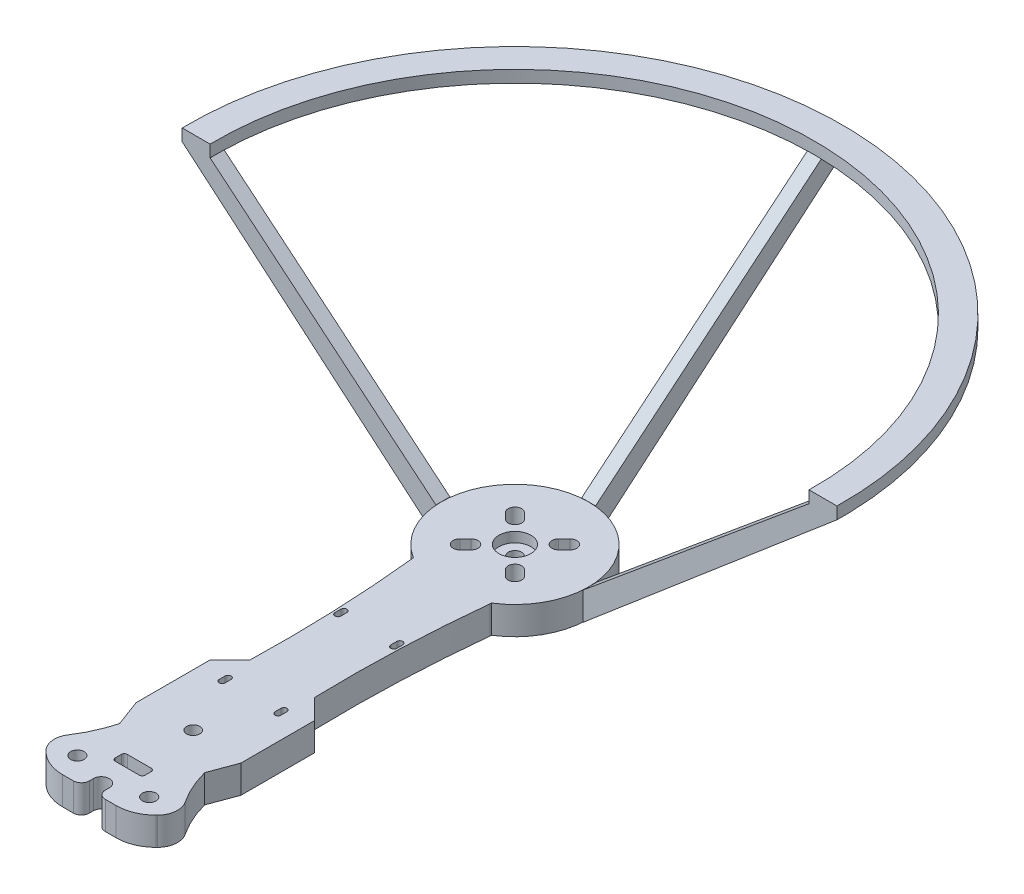
SolidWorks part; units mm, degrees
ref_plane "Front Plane" through (0, 0, 0) normal (0, 0, 1) x (1, 0, 0)
ref_plane "Top Plane" through (0, 0, 0) normal (0, 1, 0) x (1, 0, 0)
ref_plane "Right Plane" through (0, 0, 0) normal (1, 0, 0) x (0, 0, -1)
sketch "Sketch1" plane through (0, 0, 0) normal (0, 1, 0) x (1, 0, 0)
  line L1 (10, -38) -> (-10, -38)
  line L2 (10, -38) -> (10, 38)
  line L3 (10, 38) -> (-10, 38)
  line L4 (-10, -38) -> (-10, 38)
  line L5 (10, -38) -> (-10, 38) construction
  line L6 (10, 38) -> (-10, -38) construction
  point P0 (0, 0)
  dimension "D1" = 20
  dimension "D2" = 76
extrude "Boss-Extrude1" add sketch "Sketch1" along normal blind 7
sketch "Sketch2" plane through (0, 7, 0) normal (0, 1, 0) x (1, 0, 0)
  line L0 (10, 38) -> (-10, 38) construction
  line L1 (9, 69.1769) -> (-9, 69.1769)
  line L2 (-9, 69.1769) -> (-18, 53.5885)
  line L3 (-18, 53.5885) -> (-9, 38)
  line L4 (-9, 38) -> (9, 38)
  line L5 (9, 38) -> (18, 53.5885)
  line L6 (18, 53.5885) -> (9, 69.1769)
  line L7 (0, 43.2469) -> (0, 36.9227) construction
  line L8 (10, 38) -> (10, 39.7321)
  line L9 (10, 38) -> (9, 38)
  line L10 (-10, 38) -> (-9, 38)
  line L11 (-10, 38) -> (-10, 39.7321)
  line L12 (-9, 38) -> (-18, 53.5885)
  line L13 (-9, 38) -> (-18, 53.5885)
  circle A0 centre (0, 53.5885) radius 15.5885 construction
  point P13 (0, 38)
  dimension "D1" = 18
extrude "Boss-Extrude2" add sketch "Sketch2" against normal up to surface (7 mm away) up to face at (0, 0, 0)
sketch "Sketch3" plane through (0, 7, 0) normal (0, 1, 0) x (1, 0, 0)
  line L0 (-6.8943, 46.6942) -> (-5.4801, 48.1084) construction
  line L3 (-8.0964, 47.8962) -> (-6.6822, 49.3105)
  line L6 (-5.6922, 45.4921) -> (-4.278, 46.9063)
  line L9 (0, 28.0527) -> (0, 36.7379) construction
  line L12 (-6.8943, 60.4827) -> (-5.4801, 59.0685) construction
  line L13 (-5.6922, 61.6848) -> (-4.278, 60.2706)
  line L14 (-8.0964, 59.2807) -> (-6.6822, 57.8665)
  line L15 (6.8943, 60.4827) -> (5.4801, 59.0685) construction
  line L16 (8.0964, 59.2807) -> (6.6822, 57.8665)
  line L17 (5.6922, 61.6848) -> (4.278, 60.2706)
  line L18 (6.8943, 46.6942) -> (5.4801, 48.1084) construction
  line L19 (5.6922, 45.4921) -> (4.278, 46.9063)
  line L20 (8.0964, 47.8962) -> (6.6822, 49.3105)
  circle A9 centre (0, 53.5885) radius 8.75 construction
  arc A10 (-8.0964, 47.8962) -> (-5.6922, 45.4921) centre (-6.8943, 46.6942) ccw
  arc A11 (-4.278, 46.9063) -> (-6.6822, 49.3105) centre (-5.4801, 48.1084) ccw
  arc A12 (-5.6922, 61.6848) -> (-8.0964, 59.2807) centre (-6.8943, 60.4827) ccw
  arc A13 (-6.6822, 57.8665) -> (-4.278, 60.2706) centre (-5.4801, 59.0685) ccw
  arc A14 (8.0964, 59.2807) -> (5.6922, 61.6848) centre (6.8943, 60.4827) ccw
  arc A15 (4.278, 60.2706) -> (6.6822, 57.8665) centre (5.4801, 59.0685) ccw
  arc A16 (5.6922, 45.4921) -> (8.0964, 47.8962) centre (6.8943, 46.6942) ccw
  arc A17 (6.6822, 49.3105) -> (4.278, 46.9063) centre (5.4801, 48.1084) ccw
  point P4 (-6.1872, 47.4013)
  point P11 (-7.3893, 48.6034)
  point P19 (-6.1872, 59.7756)
  point P26 (6.1872, 59.7756)
  point P33 (6.1872, 47.4013)
  dimension "D1" = 17.5
  dimension "D3" = 3.4
  dimension "D4" = 45
  dimension "D2" = 2
  dimension "D5" = 4
extrude "Cut-Extrude1" cut sketch "Sketch3" against normal through all
sketch "Sketch4" plane through (0, 7, 0) normal (0, 1, 0) x (1, 0, 0)
  circle A0 centre (0, 53.5885) radius 4
  dimension "D1" = 8
extrude "Cut-Extrude2" [suppressed] cut sketch "Sketch4" against normal blind 2
sketch "Sketch5" plane through (0, 7, 0) normal (0, 1, 0) x (1, 0, 0)
  line L0 (0, -38) -> (0, -53) construction
  line L1 (-10, -38) -> (10, -38) construction
  line L2 (10, -38) -> (-10, -38)
  line L3 (-10, -38) -> (-25, -53)
  line L4 (10, -38) -> (25, -53)
  line L10 (-25, -53) -> (25, -53)
  dimension "D1" = 45
  dimension "D2" = 15
extrude "Boss-Extrude3" add sketch "Sketch5" against normal up to surface (7 mm away) up to face at (6.1872, 0, -47.4013)
hole_wizard "CSK for M3 Flat Head Machine Screw1" positions "Sketch6" profile "Sketch7" countersink size "M3" standard "ANSI Metric" end condition through all
sketch "Sketch6" plane through (0, 0, 0) normal (0, -1, 0) x (-1, 0, 0)
  line L0 (0, -53.2272) -> (0, -12.2793) construction
  line L2 (-25, -53) -> (25, -53) construction
  point P0 (9, -47)
  point P7 (-9, -47)
  dimension "D1" = 18
  dimension "D2" = 6
sketch "Sketch7" plane through (-9, 0, 47) normal (1, 0, 0) x (0, 0, -1)
  line L0 (0, 0) -> (0, 7)
  line L1 (0, 7) -> (1.7, 7)
  line L2 (1.7, 7) -> (1.7, 1.45)
  line L3 (1.7, 1.45) -> (3.15, 0)
  line L5 (3.15, 0) -> (0, 0)
  line L6 (-1.7, 1.45) -> (-3.15, 0) construction
  line L11 (0, -6.35) -> (0, 107.95) construction
  dimension "Thru Hole Dia." = 3.4
  dimension "Thru Hole Depth" = 7
  dimension "Near C'Sink Dia." = 6.3
  dimension "Near C'Sink Angle" = 90
chamfer "Chamfer3" distance 10 angle 45 2 edges at (-25, 3.5, 53) (25, 3.5, 53) first distance on face at (-17.5, 3.5, 45.5) first distance on face at (17.5, 3.5, 45.5)
chamfer "Chamfer4" distance 3 angle 45 2 edges at (-17.9289, 3.5, 53) (17.9289, 3.5, 53)
hole_wizard "Ø3.3 (3.3) Diameter Hole1" positions "Sketch9" profile "Sketch10" hole size "Ø3.3" standard "ANSI Metric" end condition through all
sketch "Sketch9" plane through (0, 0, 0) normal (0, -1, 0) x (-1, 0, 0)
  line L0 (0, 0) -> (0, -27) construction
  line L2 (9, -47) -> (-9, -47) construction
  point P0 (0, -27)
  dimension "D1" = 20
sketch "Sketch10" plane through (0, 0, 27) normal (1, 0, 0) x (0, 0, -1)
  line L0 (0, 0) -> (0, 7)
  line L1 (0, 7) -> (1.65, 7)
  line L2 (1.65, 7) -> (1.65, 0)
  line L5 (1.65, 0) -> (0, 0)
  line L11 (0, -6.35) -> (0, 107.95) construction
  dimension "Thru Hole Dia." = 3.3
  dimension "Thru Hole Depth" = 7
sketch "Sketch12" plane through (0, 7, 0) normal (0, 1, 0) x (1, 0, 0)
  line L0 (-17.9289, -45.9289) -> (-10, -32.1956)
  line L1 (-10, 39.7321) -> (-10, -38) construction
  line L2 (-10, -32.1956) -> (-10, -38)
  line L3 (-10, -38) -> (-17.9289, -45.9289)
  line L4 (0, -31.1921) -> (0, -40.6137) construction
  line L5 (10, -38) -> (17.9289, -45.9289)
  line L6 (10, -32.1956) -> (10, -38)
  line L7 (17.9289, -45.9289) -> (10, -32.1956)
  dimension "D1" = 30
extrude "Boss-Extrude4" add sketch "Sketch12" against normal through all
sketch "Sketch13" plane through (0, 0, 0) normal (0, -1, 0) x (1, 0, 0)
  line L0 (-17.9289, 45.9289) -> (-10.8579, 53)
  line L1 (14.9289, 53) -> (-14.9289, 53) construction
  line L2 (-14.9289, 53) -> (-17.9289, 50) construction
  line L3 (-10.8579, 53) -> (-14.9289, 53)
  line L4 (-14.9289, 53) -> (-17.9289, 50)
  line L5 (-17.9289, 50) -> (-17.9289, 45.9289)
  line L6 (0, 61.138) -> (0, 56.7948) construction
  line L7 (17.9289, 50) -> (17.9289, 45.9289)
  line L8 (14.9289, 53) -> (17.9289, 50)
  line L9 (10.8579, 53) -> (14.9289, 53)
  line L10 (17.9289, 45.9289) -> (10.8579, 53)
extrude "Cut-Extrude3" cut sketch "Sketch13" against normal through all
hole_wizard "Ø3.3 (3.3) Diameter Hole2" positions "Sketch15" profile "Sketch16" hole size "Ø3.3" standard "ANSI Metric" end condition through all
sketch "Sketch15" plane through (0, 7, 0) normal (0, 1, 0) x (1, 0, 0)
  point P0 (0, 53.5885)
sketch "Sketch16" plane through (0, 7, -53.5885) normal (1, 0, 0) x (0, 0, 1)
  line L0 (0, 0) -> (0, 7)
  line L1 (0, 7) -> (1.65, 7)
  line L2 (1.65, 7) -> (1.65, 0)
  line L5 (1.65, 0) -> (0, 0)
  line L11 (0, -6.35) -> (0, 107.95) construction
  dimension "Thru Hole Dia." = 3.3
  dimension "Thru Hole Depth" = 7
sketch "Sketch17" plane through (0, 7, 0) normal (0, 1, 0) x (1, 0, 0)
  line L0 (0, 43.1092) -> (0, 35.1505) construction
  line L1 (-6.25, 15.5) -> (-7.75, 18.5) construction
  line L2 (6.25, 18.5) -> (7.75, 18.5)
  line L3 (6.25, 18.5) -> (6.25, 15.5)
  line L4 (6.25, 15.5) -> (7.75, 15.5)
  line L5 (7.75, 18.5) -> (7.75, 15.5)
  line L6 (6.25, 18.5) -> (7.75, 15.5) construction
  line L7 (6.25, 15.5) -> (7.75, 18.5) construction
  line L8 (-6.25, 18.5) -> (-7.75, 15.5) construction
  line L9 (-7.75, 18.5) -> (-7.75, 15.5)
  line L10 (-6.25, 15.5) -> (-7.75, 15.5)
  line L11 (-6.25, 18.5) -> (-6.25, 15.5)
  line L12 (-6.25, 18.5) -> (-7.75, 18.5)
  line L13 (-6.3154, 6) -> (6.4912, 6) construction
  line L14 (7, 17) -> (-7, 17) construction
  point P3 (7, 17)
  point P12 (-7, 17)
  dimension "D1" = 1.5
  dimension "D2" = 3
  dimension "D3" = 14
  dimension "D4" = 17
extrude "Cut-Extrude5" cut sketch "Sketch17" against normal through all
hole_wizard "Ø4.0 (4) Diameter Hole1" positions "Sketch19" profile "Sketch20" hole size "Ø4.0" standard "ANSI Metric" end condition through all
sketch "Sketch19" plane through (0, 0, 0) normal (0, -1, 0) x (-1, 0, 0)
  line L1 (0, -53) -> (0, -50) construction
  line L2 (-10.8579, -53) -> (10.8579, -53) construction
  point P6 (0, -50)
  dimension "D1" = 3
sketch "Sketch20" plane through (0, 0, 50) normal (1, 0, 0) x (0, 0, -1)
  line L0 (0, 0) -> (0, 7)
  line L1 (0, 7) -> (2, 7)
  line L2 (2, 7) -> (2, 0)
  line L5 (2, 0) -> (0, 0)
  line L11 (0, -6.35) -> (0, 107.95) construction
  dimension "Thru Hole Dia." = 4
  dimension "Thru Hole Depth" = 7
chamfer "Chamfer5" [suppressed] distance 0.5 angle 60
sketch "Sketch22" plane through (0, 7, 0) normal (0, 1, 0) x (1, 0, 0)
  line L0 (8, 3.7682) -> (10, 3.7682) construction
  line L1 (10, -32.1956) -> (10, 39.7321) construction
  line L2 (0, 13.8796) -> (0, 7.1431) construction
  line L3 (10, 39.7321) -> (10, -32.1956)
  line L4 (-8, 3.7682) -> (-10, 3.7682) construction
  line L5 (-10, 39.7321) -> (-10, -32.1956)
  spline S0 degree 2 poles (10, -32.1956) (6, 3.7682) (10, 39.7321) knots 0 0 0 1 1 1
  spline S1 degree 2 poles (-10, -32.1956) (-6, 3.7682) (-10, 39.7321) knots 0 0 0 1 1 1
  dimension "D1" = 2
extrude "Cut-Extrude7" cut sketch "Sketch22" against normal through all
fillet "Fillet1" radius 10 4 edges at (-10, 3.5, -39.7321) (10, 3.5, -39.7321) (-10, 3.5, 32.1956) (10, 3.5, 32.1956)
fillet "Fillet4" radius 10 2 edges at (-10.8579, 3.5, 53) (10.8579, 3.5, 53)
sketch "Sketch24" plane through (0, 7, 0) normal (0, 1, 0) x (1, 0, 0)
  circle A0 centre (0, 53.5885) radius 4
  dimension "D1" = 8
extrude "Cut-Extrude9" cut sketch "Sketch24" against normal blind 2.5
sketch "Sketch25" [suppressed] plane through (0, 3.5, 0) normal (0, 1, 0) x (1, 0, 0)
  line L1 (3.2332, 54.5885) -> (1.6166, 57.3885)
  line L2 (1.6166, 57.3885) -> (-1.6166, 57.3885)
  line L3 (-1.6166, 57.3885) -> (-3.2332, 54.5885)
  line L4 (-3.2332, 54.5885) -> (-1.6166, 51.7885)
  line L5 (-1.6166, 51.7885) -> (1.6166, 51.7885)
  line L6 (1.6166, 51.7885) -> (3.2332, 54.5885)
  circle A0 centre (0, 54.5885) radius 2.8 construction
  dimension "D1" = 5.6
extrude "Cut-Extrude10" [suppressed] cut sketch "Sketch25" against normal blind 2.5
sketch "Sketch26" plane through (0, 7, 0) normal (0, 1, 0) x (1, 0, 0)
  line L0 (13.7868, -50.0711) -> (17.9289, -45.9289) construction
  line L1 (17.1511, -46.7067) -> (17.9289, -45.9289)
  line L2 (17.9289, -45.9289) -> (9.77, -30.0643)
  line L3 (13.8495, -37.9966) -> (12.0709, -38.9113) construction
  line L4 (0, -39.6423) -> (0, -36.9879) construction
  line L5 (-13.8495, -37.9966) -> (-12.0709, -38.9113) construction
  line L6 (-17.9289, -45.9289) -> (-9.77, -30.0643)
  line L7 (-17.1511, -46.7067) -> (-17.9289, -45.9289)
  arc A0 (9.77, -30.0643) -> (11.0554, -34.0237) centre (19.7157, -29.0237) ccw construction
  parabola Q7 (9.77, 37.6007) -> (9.77, -30.0643) focus (169.6747, 3.7682) apex (8, 3.7682) construction
  spline S0 degree 3 poles (9.77, -30.0643) (10.3807, -35.9011) (12.9222, -42.4779) (17.1511, -46.7067) knots 0 0 0 0 1 1 1 1
  spline S1 degree 3 poles (-9.77, -30.0643) (-10.3807, -35.9011) (-12.9222, -42.4779) (-17.1511, -46.7067) knots 0 0 0 0 1 1 1 1
  dimension "D1" = 1.1
  dimension "D2" = 2
extrude "Cut-Extrude11" cut sketch "Sketch26" against normal through all
fillet "Fillet6" radius 5 2 edges at (-17.1511, 3.5, 46.7067) (17.1511, 3.5, 46.7067)
sketch "Sketch27" plane through (0, 0, 0) normal (0, -1, 0) x (1, 0, 0)
  line L0 (0, -41.8385) -> (0, -8.9192) construction
  line L1 (4, -41.8385) -> (-4, -41.8385)
  line L2 (4, -41.8385) -> (4, 24)
  line L3 (4, 24) -> (-4, 24)
  line L4 (-4, -41.8385) -> (-4, 24)
  line L5 (4, -41.8385) -> (-4, 24) construction
  line L6 (4, 24) -> (-4, -41.8385) construction
  line L7 (2.1644, 24) -> (8.503, 34)
  line L8 (8.503, 34) -> (10.4529, 34)
  line L9 (9.77, 30.0643) -> (4, 18.1842)
  line L10 (-9.77, 30.0643) -> (-4, 18.1842)
  line L11 (-8.503, 34) -> (-10.4529, 34)
  line L12 (-2.1644, 24) -> (-8.503, 34)
  arc A0 (-2.9037, 25.1664) -> (3.3528, 25.8748) centre (0.0525, 27.0402) ccw
  spline S0 degree 3 poles (9.77, 30.0643) (10.2443, 34.5975) (11.8833, 39.5771) (14.5729, 43.5564) knots 0 0 0 0 0.776665 0.776665 0.776665 0.776665 construction
  spline S2 degree 3 poles (-9.77, 30.0643) (-10.2443, 34.5975) (-11.8833, 39.5771) (-14.5729, 43.5564) knots 0 0 0 0 0.776665 0.776665 0.776665 0.776665
  spline S3 degree 3 poles (957.257, 3909.3873) (-557.8084, -4132.4571) (127.9512, 4231.1248) (418.084, -3925.1081) knots -10.727138 -10.727138 -10.727138 -10.727138 11.282901 11.282901 11.282901 11.282901 only from (9.77, 30.0643) to (14.5729, 43.5564)
  spline S4 degree 3 poles (9.77, 30.0643) (10.2443, 34.5975) (11.8833, 39.5771) (14.5729, 43.5564) knots 0 0 0 0 0.776665 0.776665 0.776665 0.776665
  point P0 (0, -8.9192)
  point P19 (0, -44.8385)
  spline M15 degree 3 poles (-17.1511, 46.7067) (-12.9222, 42.4779) (-10.3807, 35.9011) (-9.77, 30.0643) knots 0 0 0 0 1 1 1 1 only from (-14.5729, 43.5564) to (-9.77, 30.0643)
  spline M25 degree 3 poles (9.77, 30.0643) (10.3807, 35.9011) (12.9222, 42.4779) (17.1511, 46.7067) knots 0 0 0 0 1 1 1 1 only from (9.77, 30.0643) to (14.5729, 43.5564)
  dimension "D2" = 8
  dimension "D3" = 0
  dimension "D4" = 3
  dimension "D6" = 10
  dimension "D7" = 25.905
extrude "Boss-Extrude5" [suppressed] add sketch "Sketch27" along normal blind 5 contours L3 L12 L11 L10 L4 M15 | L9 L8 L7 L3 L2 M25 | L4 L1 L2 L3 | A0 L3 L7
chamfer "Chamfer6" [suppressed] distance 5 angle 45
chamfer "Chamfer7" [suppressed] distance 1.1 angle 60
sketch "Sketch28" plane through (0, 0, 0) normal (0, -1, 0) x (1, 0, 0)
  line L1 (-6.25, -15.5) -> (6.25, -15.5)
  line L2 (-6.25, -15.5) -> (-6.25, -18.5)
  line L3 (-6.25, -18.5) -> (6.25, -18.5)
  line L4 (6.25, -15.5) -> (6.25, -18.5)
extrude "Cut-Extrude12" [suppressed] cut sketch "Sketch28" along normal blind 2
fillet "Fillet7" [suppressed] radius 1
sketch "Sketch29" plane through (0, 0, 0) normal (0, -1, 0) x (1, 0, 0)
  line L1 (-6.25, -15.5) -> (6.25, -15.5)
  line L2 (-6.25, -15.5) -> (-6.25, -18.5)
  line L3 (-6.25, -18.5) -> (6.25, -18.5)
  line L4 (6.25, -15.5) -> (6.25, -18.5)
extrude "Cut-Extrude13" [suppressed] cut sketch "Sketch29" against normal blind 2
sketch "Sketch30" plane through (0, 0, 0) normal (0, -1, 0) x (1, 0, 0)
  line L0 (4.5, 38.6766) -> (4.5, -37.6008)
  line L1 (0, 13.6383) -> (0, -11.8344) construction
  line L2 (-4.5, 38.6766) -> (-4.5, -37.6008)
  line L3 (4.5, -37.6008) -> (9.77, -37.6008)
  line L5 (-4.5, -37.6008) -> (-9.77, -37.6008)
  line L7 (11.9725, 38.6766) -> (4.5, 38.6766)
  line L8 (-11.9725, 38.6766) -> (-4.5, 38.6766)
  arc A0 (9.77, -37.6007) -> (11.0554, -41.5601) centre (19.7157, -36.5601) ccw construction
  parabola Q1 (-9.77, -37.6008) -> (-9.77, 30.0643) focus (-232.0942, -2.8465) apex (-8.494, -1.93)
  parabola Q3 (9.77, -37.6008) -> (9.77, 30.0643) focus (232.0942, -2.8465) apex (8.494, -1.93)
  parabola Q5 (9.77, -37.6007) -> (9.77, 30.0643) focus (169.6747, -3.7682) apex (8, -3.7682) construction
  spline S1 degree 3 poles (-9.77, 30.0643) (-10.2443, 34.5975) (-11.8833, 39.5771) (-14.5729, 43.5564) knots 0 0 0 0 0.776665 0.776665 0.776665 0.776665
  spline S2 degree 3 poles (957.257, 3909.3873) (-557.8084, -4132.4571) (127.9512, 4231.1248) (418.084, -3925.1081) knots -10.727138 -10.727138 -10.727138 -10.727138 11.282901 11.282901 11.282901 11.282901 only from (9.77, 30.0643) to (14.5729, 43.5564)
  spline S3 degree 3 poles (9.77, 30.0643) (10.2443, 34.5975) (11.8833, 39.5771) (14.5729, 43.5564) knots 0 0 0 0 0.776665 0.776665 0.776665 0.776665
  line M6 (-7.75, -18.5) -> (-7.75, -15.5)
  line M8 (7.75, -15.5) -> (7.75, -18.5)
  spline M13 degree 3 poles (-17.1511, 46.7067) (-12.9222, 42.4779) (-10.3807, 35.9011) (-9.77, 30.0643) knots 0 0 0 0 1 1 1 1 only from (-14.5729, 43.5564) to (-9.77, 30.0643)
  spline M14 degree 2 poles (-10, 32.1956) (-6, -3.7682) (-10, -39.7321) knots 0 0 0 1 1 1 only from (-9.77, 30.0643) to (-9.77, -37.6007)
  arc M15 (-9.77, -37.6007) -> (-11.0554, -41.5601) centre (-19.7157, -36.5601) cw
  arc M21 (11.0554, -41.5601) -> (9.77, -37.6007) centre (19.7157, -36.5601) cw
  spline M22 degree 2 poles (10, -39.7321) (6, -3.7682) (10, 32.1956) knots 0 0 0 1 1 1 only from (9.77, -37.6007) to (9.77, 30.0643)
  spline M23 degree 3 poles (9.77, 30.0643) (10.3807, 35.9011) (12.9222, 42.4779) (17.1511, 46.7067) knots 0 0 0 0 1 1 1 1 only from (9.77, 30.0643) to (14.5729, 43.5564)
  dimension "D1" = 9
  dimension "D3" = 0
extrude "Boss-Extrude6" [suppressed] add sketch "Sketch30" along normal blind 4 contours Q3 L7 L0 L3 M22 M23 M8 M21 | Q1 L5 L2 L8 M14 M15 M6 M13
fillet "Fillet8" radius 0.75 8 edges at (7.75, 3.5, -18.5) (6.25, 3.5, -18.5) (7.75, 3.5, -15.5) (6.25, 3.5, -15.5) (-7.75, 3.5, -18.5) (-7.75, 3.5, -15.5) (-6.25, 3.5, -15.5) (-6.25, 3.5, -18.5)
chamfer "Chamfer9" [suppressed] distance 1 angle 60
chamfer "Chamfer10" [suppressed] distance 0.7 angle 60
sketch "Sketch32" plane through (0, 0, 0) normal (0, -1, 0) x (1, 0, 0)
  line L0 (2, 50) -> (2, 53)
  line L1 (6.7157, 53) -> (-6.7157, 53) construction
  line L2 (2, 53) -> (-2, 53)
  line L3 (-2, 53) -> (-2, 50)
  circle A0 centre (0, 50) radius 2 construction
  arc A1 (-2, 50) -> (2, 50) centre (0, 50) cw
extrude "Cut-Extrude14" cut sketch "Sketch32" against normal through all
fillet "Fillet10" radius 2 2 edges at (2, 3.5, 53) (-2, 3.5, 53)
sketch "Sketch33" plane through (0, 7, 0) normal (0, 1, 0) x (1, 0, 0)
  line L0 (-13.113, -28.1513) -> (-10.6516, -34.7802)
  line L1 (-13.113, -28.1513) -> (-13.113, -9.7802)
  line L2 (-13.113, -9.7802) -> (-8.113, -4.7802)
  line L3 (-10.6516, -34.7802) -> (-8.6702, -31.1191)
  line L4 (-8.6702, -31.1191) -> (-8.113, -4.7802)
  line L5 (-6.7157, -53) -> (-4, -53) construction
  parabola Q0 (-9.77, -30.0643) -> (-9.77, 37.6007) focus (-169.6747, 3.7682) apex (-8, 3.7682) construction
  spline S2 degree 3 poles (-14.5729, -43.5564) (-11.8833, -39.5771) (-10.2443, -34.5975) (-9.77, -30.0643) knots 0.223335 0.223335 0.223335 0.223335 1 1 1 1 construction
  dimension "D1" = 18.2198
  dimension "D2" = 135
  dimension "D4" = 5
  dimension "D6" = 30
extrude "Boss-Extrude7" add sketch "Sketch33" against normal through all
sketch "Sketch35" plane through (0, 7, 0) normal (0, 1, 0) x (1, 0, 0)
  line L0 (0, -24.4986) -> (0, -33.0373) construction
  line L1 (-2.25, -43.5) -> (-3.75, -40.5) construction
  line L2 (2.25, -40.5) -> (3.75, -40.5)
  line L3 (2.25, -40.5) -> (2.25, -43.5)
  line L4 (2.25, -43.5) -> (3.75, -43.5)
  line L5 (3.75, -40.5) -> (3.75, -43.5)
  line L6 (2.25, -40.5) -> (3.75, -43.5) construction
  line L7 (2.25, -43.5) -> (3.75, -40.5) construction
  line L8 (-2.25, -40.5) -> (-3.75, -43.5) construction
  line L9 (-3.75, -40.5) -> (-3.75, -43.5)
  line L10 (-2.25, -43.5) -> (-3.75, -43.5)
  line L11 (-2.25, -40.5) -> (-2.25, -43.5)
  line L12 (-2.25, -40.5) -> (-3.75, -40.5)
  line L14 (3, -42) -> (-3, -42) construction
  arc A0 (2, -50) -> (-2, -50) centre (0, -50) ccw construction
  point P3 (3, -42)
  point P12 (-3, -42)
  dimension "D4" = 8
  dimension "D1" = 1.5
  dimension "D2" = 3
  dimension "D3" = 6
extrude "Cut-Extrude15" cut sketch "Sketch35" against normal through all
sketch "Sketch36" plane through (0, 7, 0) normal (0, 1, 0) x (1, 0, 0)
  line L1 (-2.25, -40.5) -> (2.25, -40.5)
  line L2 (-2.25, -40.5) -> (-2.25, -43.5)
  line L3 (-2.25, -43.5) -> (2.25, -43.5)
  line L4 (2.25, -40.5) -> (2.25, -43.5)
extrude "Cut-Extrude16" cut sketch "Sketch36" against normal blind 3
fillet "Fillet11" radius 0.75 8 edges at (-3.75, 3.5, 43.5) (-2.25, 2, 40.5) (-2.25, 2, 43.5) (2.25, 2, 43.5) (2.25, 2, 40.5) (3.75, 3.5, 40.5) (3.75, 3.5, 43.5) (-3.75, 3.5, 40.5)
mirror "Mirror6" about plane through (0, 0, 0) normal (1, 0, 0) of "Boss-Extrude7"
sketch "Sketch37" plane through (0, 7, 0) normal (0, 1, 0) x (1, 0, 0)
  line L0 (0, -2.5332) -> (0, -11.0718) construction
  line L1 (-6.25, -13.5) -> (-7.75, -10.5) construction
  line L2 (6.25, -10.5) -> (7.75, -10.5)
  line L3 (6.25, -10.5) -> (6.25, -13.5)
  line L4 (6.25, -13.5) -> (7.75, -13.5)
  line L5 (7.75, -10.5) -> (7.75, -13.5)
  line L6 (6.25, -10.5) -> (7.75, -13.5) construction
  line L7 (6.25, -13.5) -> (7.75, -10.5) construction
  line L8 (-6.25, -10.5) -> (-7.75, -13.5) construction
  line L9 (-7.75, -10.5) -> (-7.75, -13.5)
  line L10 (-6.25, -13.5) -> (-7.75, -13.5)
  line L11 (-6.25, -10.5) -> (-6.25, -13.5)
  line L12 (-6.25, -10.5) -> (-7.75, -10.5)
  line L14 (7, -12) -> (-7, -12) construction
  circle A1 centre (0, -27) radius 1.65 construction
  point P3 (7, -12)
  point P12 (-7, -12)
  dimension "D4" = 15
  dimension "D1" = 1.5
  dimension "D2" = 3
  dimension "D3" = 14
extrude "Cut-Extrude17" cut sketch "Sketch37" against normal through all
fillet "Fillet12" radius 0.75 8 edges at (6.25, 3.5, 13.5) (7.75, 3.5, 10.5) (7.75, 3.5, 13.5) (6.25, 3.5, 10.5) (-7.75, 3.5, 13.5) (-6.25, 3.5, 10.5) (-6.25, 3.5, 13.5) (-7.75, 3.5, 10.5)
fillet "Fillet13" [suppressed] radius 5
fillet "Fillet14" [suppressed] radius 3
fillet "Fillet15" radius 3 4 edges at (-18, 3.5, -53.5885) (-9, 3.5, -69.1769) (9, 3.5, -69.1769) (18, 3.5, -53.5885)
chamfer "Chamfer12" [suppressed] distance 2 angle 45
fillet "Fillet16" [suppressed] radius 2
chamfer "Chamfer13" [suppressed] distance 2 angle 45
sketch "Sketch38" [suppressed] plane through (0, -4, 0) normal (0, -1, 0) x (1, 0, 0)
  circle A0 centre (0, 27) radius 4.25
  dimension "D1" = 8.5
extrude "Cut-Extrude18" [suppressed] cut sketch "Sketch38" against normal up to surface (4 mm away)
hole_wizard "Ø3.3 (3.3) Diameter Hole4" [suppressed] positions "Sketch39" profile "Sketch40" hole size "Ø3.3" standard "ANSI Metric"
sketch "Sketch39" plane through (0, 7, 0) normal (0, 1, 0) x (1, 0, 0)
  point P0 (0, 23)
sketch "Sketch40" plane through (0, 7, -23) normal (1, 0, 0) x (0, 0, 1)
  line L0 (0, 0) -> (0, 7)
  line L1 (0, 7) -> (1.65, 7)
  line L2 (1.65, 7) -> (1.65, 0)
  line L5 (1.65, 0) -> (0, 0)
  line L11 (0, -6.35) -> (0, 107.95) construction
  dimension "Thru Hole Dia." = 3.3
  dimension "Thru Hole Depth" = 7
sketch "Sketch41" [suppressed] plane through (0, 7, 0) normal (0, 1, 0) x (1, 0, 0)
  line L1 (3.2332, 23) -> (1.6166, 25.8)
  line L2 (1.6166, 25.8) -> (-1.6166, 25.8)
  line L3 (-1.6166, 25.8) -> (-3.2332, 23)
  line L4 (-3.2332, 23) -> (-1.6166, 20.2)
  line L5 (-1.6166, 20.2) -> (1.6166, 20.2)
  line L6 (1.6166, 20.2) -> (3.2332, 23)
  circle A0 centre (0, 23) radius 2.8 construction
  dimension "D1" = 5.6
extrude "Cut-Extrude19" [suppressed] cut sketch "Sketch41" against normal blind 2
sketch "Sketch42" plane through (0, 7, 0) normal (0, 1, 0) x (1, 0, 0)
  line L17 (-9.866, 67.6769) -> (-17.134, 55.0885)
  line L18 (-17.134, 52.0885) -> (-11.0554, 41.5601)
  line L19 (-8.113, -4.7802) -> (-13.113, -9.7802)
  line L20 (-13.113, -9.7802) -> (-13.113, -28.1513)
  line L21 (-13.113, -28.1513) -> (-10.6516, -34.7802)
  line L22 (-13.966, -49.8919) -> (-13.7868, -50.0711)
  line L23 (-6.7157, -53) -> (-4, -53)
  line L24 (-2, -51) -> (-2, -50)
  line L25 (2, -50) -> (2, -51)
  line L26 (4, -53) -> (6.7157, -53)
  line L27 (13.7868, -50.0711) -> (13.966, -49.8919)
  line L28 (10.6516, -34.7802) -> (13.113, -28.1513)
  line L29 (13.113, -28.1513) -> (13.113, -9.7802)
  line L30 (13.113, -9.7802) -> (8.113, -4.7802)
  line L31 (11.0554, 41.5601) -> (17.134, 52.0885)
  line L32 (17.134, 55.0885) -> (9.866, 67.6769)
  line L33 (7.2679, 69.1769) -> (-7.2679, 69.1769)
  line L34 (-9.866, 67.6769) -> (-17.134, 55.0885)
  line L35 (-17.134, 52.0885) -> (-11.0554, 41.5601)
  line L48 (11.0554, 41.5601) -> (17.134, 52.0885)
  line L49 (17.134, 55.0885) -> (9.866, 67.6769)
  line L50 (7.2679, 69.1769) -> (-7.2679, 69.1769)
  arc A0 (9.8153, 37.968) -> (-9.8153, 37.968) centre (0, 53.5885) ccw
  arc A13 (-17.134, 55.0885) -> (-17.134, 52.0885) centre (-14.5359, 53.5885) ccw
  arc A14 (-9.77, 37.6007) -> (-11.0554, 41.5601) centre (-19.7157, 36.5601) ccw
  arc A15 (-14.5729, -43.5564) -> (-13.966, -49.8919) centre (-10.4304, -46.3564) ccw
  arc A16 (-13.7868, -50.0711) -> (-6.7157, -53) centre (-6.7157, -43) ccw
  arc A17 (-4, -53) -> (-2, -51) centre (-4, -51) ccw
  arc A18 (2, -50) -> (-2, -50) centre (0, -50) ccw
  arc A19 (2, -51) -> (4, -53) centre (4, -51) ccw
  arc A20 (6.7157, -53) -> (13.7868, -50.0711) centre (6.7157, -43) ccw
  arc A21 (13.966, -49.8919) -> (14.5729, -43.5564) centre (10.4304, -46.3564) ccw
  arc A22 (11.0554, 41.5601) -> (9.77, 37.6007) centre (19.7157, 36.5601) ccw
  arc A23 (17.134, 52.0885) -> (17.134, 55.0885) centre (14.5359, 53.5885) ccw
  arc A24 (9.866, 67.6769) -> (7.2679, 69.1769) centre (7.2679, 66.1769) ccw
  arc A25 (-7.2679, 69.1769) -> (-9.866, 67.6769) centre (-7.2679, 66.1769) ccw
  arc A26 (-17.134, 55.0885) -> (-17.134, 52.0885) centre (-14.5359, 53.5885) ccw
  arc A27 (-9.8153, 37.968) -> (-11.0554, 41.5601) centre (-19.7157, 36.5601) ccw
  arc A35 (11.0554, 41.5601) -> (9.8153, 37.968) centre (19.7157, 36.5601) ccw
  arc A36 (17.134, 52.0885) -> (17.134, 55.0885) centre (14.5359, 53.5885) ccw
  arc A37 (9.866, 67.6769) -> (7.2679, 69.1769) centre (7.2679, 66.1769) ccw
  arc A38 (-7.2679, 69.1769) -> (-9.866, 67.6769) centre (-7.2679, 66.1769) ccw
  parabola Q2 (-9.77, 37.6007) -> (-8.113, -4.7802) focus (-169.6747, 3.7682) apex (-8, 3.7682)
  parabola Q3 (8.113, -4.7802) -> (9.77, 37.6007) focus (169.6747, 3.7682) apex (8, 3.7682)
  spline S2 degree 3 poles (-340.2921, -978.8864) (178.8418, 1086.1877) (-14.5594, -1163.0256) (-237.7548, 931.208) knots -6.82744 -6.82744 -6.82744 -6.82744 7.27343 7.27343 7.27343 7.27343 only from (-10.6516, -34.7802) to (-14.5729, -43.5564)
  spline S3 degree 3 poles (237.7561, 931.2201) (14.5605, -1163.0302) (-178.842, 1086.1829) (340.2891, -978.8743) knots -6.273457 -6.273457 -6.273457 -6.273457 7.827413 7.827413 7.827413 7.827413 only from (14.5729, -43.5564) to (10.6516, -34.7802)
  dimension "D1" = 0
extrude "Boss-Extrude8" add sketch "Sketch42" against normal up to surface (7 mm away) contours A0 A27 L35 A26 L34 A38 L50 A37 L49 A36 L48 A35 up to face at (7, 0, 12)
ref_plane "Plane1" through (0, 0, -54) normal (0, 0, 1) x (1, 0, 0)
sketch "Sketch44" plane through (0, 0, -54) normal (0, 0, 1) x (1, 0, 0)
  line L0 (-18.4483, 7) -> (-18.4483, 0)
  line L1 (-18.4483, 7) -> (-18.4483, 57) construction
  line L2 (0, 7) -> (0, 57) construction
  line L3 (18.4483, 7) -> (-18.4483, 7) construction
  line L5 (-18.4483, 7) -> (-75, 54)
  line L6 (-75, 57) -> (-75, 54) construction
  line L7 (-75, 54) -> (-82, 54)
  line L9 (75, 57) -> (75, 54) construction
  line L10 (18.4483, 7) -> (18.4483, 57) construction
  line L12 (75, 54) -> (82, 54)
  line L13 (18.4483, 7) -> (75, 54)
  line L14 (18.4483, 7) -> (18.4483, 0)
  line L15 (-18.4483, 0) -> (-82, 54)
  line L16 (18.4483, 0) -> (82, 54)
  line L17 (75, 54) -> (-75, 54) construction
  line L18 (0, 7) -> (0, 52) construction
  line L19 (0, 52) -> (-70, 52) construction
  dimension "D1" = 50
  dimension "D2" = 150
  dimension "D3" = 3
  dimension "D4" = 7
  dimension "D5" = 0
  dimension "D6" = 45
  dimension "D7" = 70
extrude "Boss-Extrude9" add sketch "Sketch44" along normal mid plane 3.5 separate body
ref_plane "Plane2" through (1.65, 0, 0) normal (-1, 0, 0) x (0, 1, 0)
ref_plane "Plane3" through (0, 0, 0) normal (-1, 0, 0) x (0, 1, 0)
sketch "Sketch47" plane through (0, 54, 0) normal (0, 1, 0) x (1, 0, 0)
  line L3 (-75, 52.25) -> (-82, 52.25)
  line L4 (75, 52.25) -> (82, 52.25)
  arc A6 (82, 52.25) -> (-82, 52.25) centre (0, 53.5885) ccw
  arc A7 (75, 52.25) -> (-75, 52.25) centre (0, 53.5885) ccw
extrude "Boss-Extrude11" add sketch "Sketch47" along normal blind 3
sketch "Sketch45" plane through (0, 0, 0) normal (-1, 0, 0) x (0, 1, 0)
  line L0 (0, 72.0367) -> (54, 135.5994)
  line L10 (7, 72.0367) -> (54, 128.5994)
  line L28 (7, 79.3675) -> (7, 128.5885) construction
  line L30 (7, 72.0367) -> (0, 72.0367)
  line L31 (54, 128.5994) -> (54, 135.5994)
  dimension "D1" = 7
  dimension "D2" = 0
extrude "Boss-Extrude12" add sketch "Sketch45" along normal mid plane 3.5 contours L0 L31 L10 L30
sketch "Sketch48" plane through (0, 0, 0) normal (-1, 0, 0) x (0, 1, 0)
  line L3 (57, 55.0024) -> (54, 55.0024)
  line L8 (57, 52.25) -> (57, 135.5994) construction
  line L11 (54, 135.5807) -> (54, 55.75) construction
  line L16 (54, 128.5994) -> (57, 128.4755)
  line L17 (57, 128.4755) -> (57, 55.0024)
  line L18 (54, 128.5994) -> (54, 55.0024)
